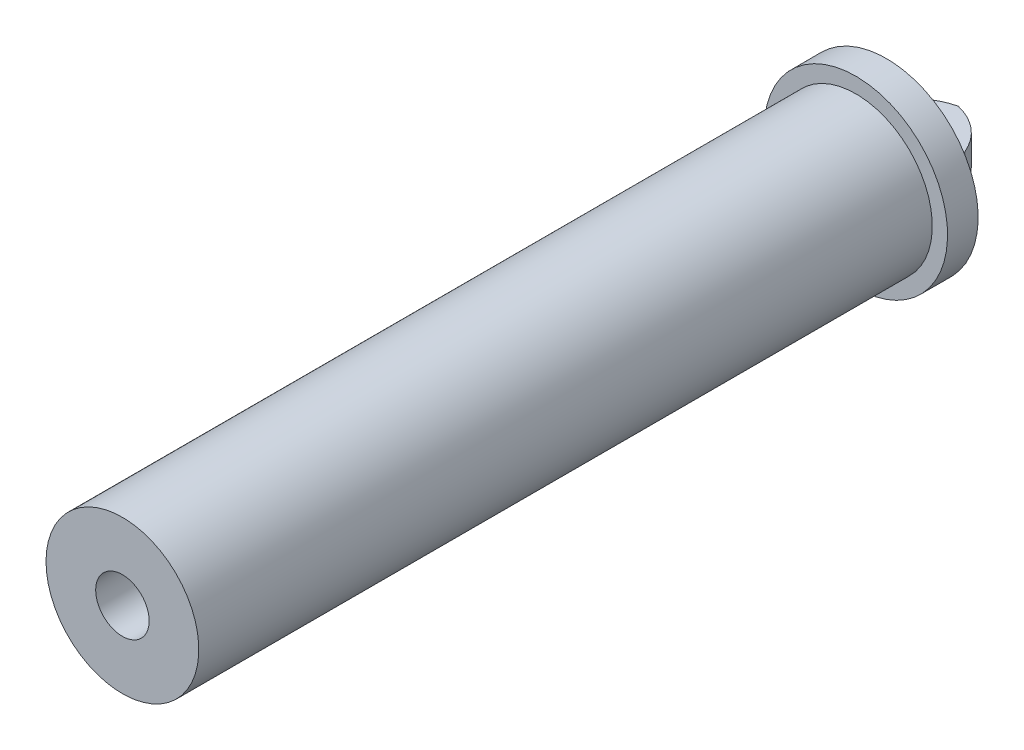
SolidWorks part; units mm, degrees
material "6061 Alloy"
ref_plane "Front Plane" through (0, 0, 0) normal (0, 0, 1) x (1, 0, 0)
ref_plane "Top Plane" through (0, 0, 0) normal (0, 1, 0) x (1, 0, 0)
ref_plane "Right Plane" through (0, 0, 0) normal (1, 0, 0) x (0, 0, -1)
sketch "Sketch1" plane through (0, 0, 0) normal (0, 0, 1) x (1, 0, 0)
  circle A0 centre (0, 0) radius 31.75
  circle A1 centre (0, 0) radius 11.1125
  dimension "D1" = 63.5
  dimension "D2" = 22.225
extrude "Boss-Extrude1" add sketch "Sketch1" along normal blind 304.8
ref_plane "Plane1" through (0, 0, 0) normal (0, 0, -1) x (-1, 0, 0)
sketch "Sketch2" plane through (0, 0, 0) normal (0, 0, -1) x (-1, 0, 0)
  circle A0 centre (0, 0) radius 38.1
  dimension "D1" = 76.2
extrude "Boss-Extrude2" add sketch "Sketch2" along normal blind 12.7
ref_plane "Plane2" through (0, 0, -12.7) normal (0, 0, -1) x (-1, 0, 0)
sketch "Sketch3" plane through (0, 0, -12.7) normal (0, 0, -1) x (-1, 0, 0)
  line L1 (-19.6845, 6.0211) -> (19.6845, 6.0211)
  line L2 (-19.6845, 6.0211) -> (-19.6845, -6.0211)
  line L3 (-19.6845, -6.0211) -> (19.6845, -6.0211)
  line L4 (19.6845, 6.0211) -> (19.6845, -6.0211)
  line L5 (-19.6845, 6.0211) -> (19.6845, -6.0211) construction
  line L6 (-19.6845, -6.0211) -> (19.6845, 6.0211) construction
  point P0 (0, 0)
extrude "Boss-Extrude3" add sketch "Sketch3" along normal blind 30.48
fillet "Fillet1" radius 25.4 2 edges at (-19.6845, 0, -43.18) (19.6845, 0, -43.18)
ref_plane "Plane3" through (0, -6.0211, 0) normal (0, -1, 0) x (-1, 0, 0)
sketch "Sketch4" plane through (0, -6.0211, 0) normal (0, -1, 0) x (-1, 0, 0)
  line L0 (0, 42.5286) -> (0, 12.7) construction
  line L1 (17.6434, 12.7) -> (-17.6434, 12.7) construction
  circle A0 centre (0, 27.6143) radius 6.35
  dimension "D1" = 12.7
extrude "Cut-Extrude1" cut sketch "Sketch4" against normal through all
fillet "Fillet2" radius 25.4 2 edges at (-19.6845, 0, -12.7) (19.6845, 0, -12.7)
